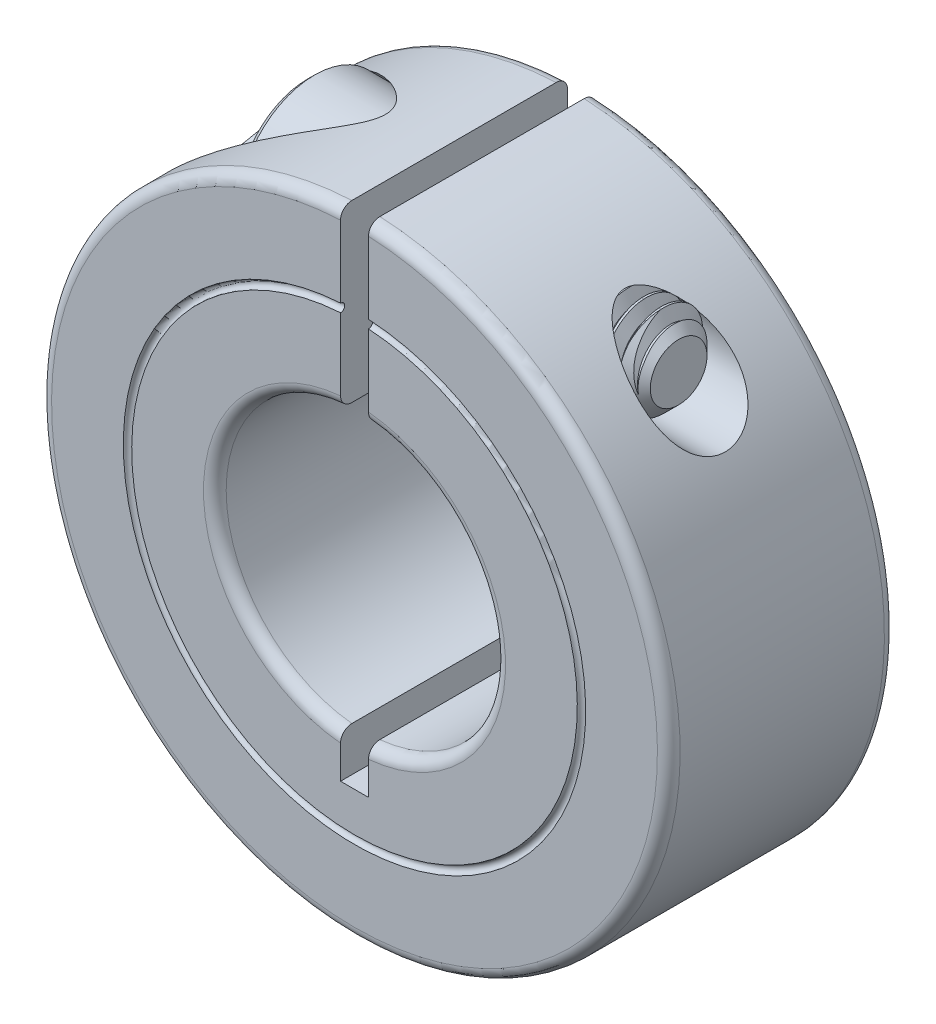
SolidWorks part; units mm, degrees
ref_plane "Front Plane" through (0, 0, 0) normal (0, 0, 1) x (1, 0, 0)
ref_plane "Top Plane" through (0, 0, 0) normal (0, 1, 0) x (1, 0, 0)
ref_plane "Right Plane" through (0, 0, 0) normal (1, 0, 0) x (0, 0, -1)
sketch "Sketch1" plane through (0, 0, 0) normal (0, 0, 1) x (1, 0, 0)
  line L0 (-0.635, 6.3182) -> (-0.635, 14.2734)
  line L2 (0.635, 6.3182) -> (0.635, 14.2734)
  line L3 (0, 0) -> (0, 6.3182) construction
  line L4 (0.635, 6.3182) -> (-0.635, 6.3182) construction
  line L5 (0, -14.2875) -> (0, -6.35) construction
  line L6 (0, -6.35) -> (0, -10.3188) construction
  line L7 (-0.635, -6.3182) -> (-0.635, -8.3344)
  line L8 (-0.635, -8.3344) -> (0.635, -8.3344)
  line L9 (0.635, -6.3182) -> (0.635, -8.3344)
  line L10 (-0.635, 10.2958) -> (0.635, 10.2958) construction
  circle A0 centre (0, 0) radius 14.2875 construction
  circle A1 centre (0, 0) radius 6.35 construction
  arc A3 (-0.635, 14.2734) -> (0.635, 14.2734) centre (0, 0) ccw
  arc A4 (0.635, -6.3182) -> (0.635, 6.3182) centre (0, 0) ccw
  arc A5 (-0.635, 6.3182) -> (-0.635, -6.3182) centre (0, 0) ccw
  point P4 (14.2875, 0)
  point P5 (-14.2875, 0)
  point P19 (0, -8.3344)
  dimension "Bore Dia" = 12.7
  dimension "OD" = 28.575
  dimension "Separation" = 1.27
extrude "Extrude1" add sketch "Sketch1" along normal mid plane 10.3187
fillet "Fillet1" radius 0.5159 6 edges at (0, -14.2875, -5.1594) (0, -14.2875, 5.1594) (-6.35, 0, 5.1594) (-6.35, 0, -5.1594) (6.35, 0, 5.1594) (6.35, 0, -5.1594)
sketch "Sketch2" plane through (0, 0, 0) normal (0, 1, 0) x (1, 0, 0)
  line L0 (0, 0) -> (-6.35, 0) construction
  line L1 (-6.35, 0) -> (-14.2875, 0) construction
  line L2 (-10.3188, 5.1594) -> (-10.3188, -5.1594) construction
  line L3 (13.7716, 5.1594) -> (-13.7716, 5.1594) construction
  line L4 (-13.7716, -5.1594) -> (13.7716, -5.1594) construction
  line L5 (-14.2875, 4.6434) -> (-14.2875, -4.6434) construction
  line L6 (-6.35, 4.6434) -> (-6.35, -4.6434) construction
  line L8 (-10.5092, -5.1594) -> (-10.1283, -5.1594)
  line L9 (0, 5.1594) -> (0, -5.1594) construction
  line L10 (-0.635, 5.1594) -> (-6.8659, 5.1594) construction
  arc A1 (-10.1283, -5.1594) -> (-10.5092, -5.1594) centre (-10.3188, -5.1594) ccw
  point P1 (-10.3188, 0)
  dimension "D2" = 0.1905
revolve "Cut-Revolve1" cut sketch "Sketch2" angle 360 about L9
sketch "Sketch3" plane through (0, 0, 0) normal (0, 0, 1) x (1, 0, 0)
  line L0 (14.2875, 10.2958) -> (-14.2875, 10.2958)
  line L1 (-14.2875, 10.2958) -> (-14.2875, 6.8033)
  line L2 (-14.2875, 6.8033) -> (-3.1242, 6.8033)
  line L4 (-3.1242, 6.8033) -> (-3.1242, 8.213)
  line L7 (-3.1242, 8.213) -> (14.2875, 8.213)
  line L8 (14.2875, 8.213) -> (14.2875, 10.2958)
  line L9 (-14.2875, 10.2958) -> (-17.78, 10.2958) construction
  line L10 (-0.635, 10.2958) -> (0.635, 10.2958) construction
  dimension "D2" = 3.1242
  dimension "D4" = 6.985
  dimension "Screw Dia" = 4.1656
revolve "Cut-Revolve2" cut sketch "Sketch3" angle 360 about L9
sketch "Sketch4" plane through (0, 0, 0) normal (0, 0, 1) x (1, 0, 0)
  line L0 (-7.2898, 10.2958) -> (-7.2898, 13.7248)
  line L2 (-7.2898, 13.7248) -> (-3.1242, 13.7248)
  line L3 (-3.1242, 13.7248) -> (-3.1242, 12.3786)
  line L4 (-3.1242, 12.3786) -> (9.5758, 12.3786)
  line L5 (-3.1242, 6.8033) -> (-3.1242, 8.213) construction
  line L6 (9.5758, 12.3786) -> (9.5758, 10.2958)
  line L7 (-3.1242, 8.213) -> (14.2875, 8.213) construction
  line L8 (9.5758, 10.2958) -> (-7.2898, 10.2958)
  line L9 (9.5758, 12.3786) -> (9.5758, 8.213) construction
  line L10 (-7.2898, 10.2958) -> (-10.7188, 10.2958) construction
  line L11 (-14.2875, 10.2958) -> (-17.78, 10.2958) construction
  dimension "Head Ht" = 4.1656
  dimension "Screw Lg" = 12.7
  dimension "Head Dia" = 6.858
revolve "Revolve1" add sketch "Sketch4" angle 360 about L8
sketch "Sketch5" plane through (-7.2898, 0, 0) normal (-1, 0, 0) x (0, -1, 0)
  line L1 (-9.2647, -1.7859) -> (-8.2336, 0)
  line L2 (-8.2336, 0) -> (-9.2647, 1.7859)
  line L3 (-9.2647, 1.7859) -> (-11.3269, 1.7859)
  line L4 (-11.3269, 1.7859) -> (-12.358, 0)
  line L5 (-12.358, 0) -> (-11.3269, -1.7859)
  line L6 (-11.3269, -1.7859) -> (-9.2647, -1.7859)
  circle A0 centre (-10.2958, 0) radius 1.7859 construction
  dimension "Hex" = 3.5719
extrude "Cut-Extrude1" cut sketch "Sketch5" against normal blind 3.5719
chamfer "Chamfer1" distance 0.3175 angle 45 1 edges at (-7.2898, 13.7248, 0)
sketch "Sketch6" plane through (9.5758, 0, 0) normal (1, 0, 0) x (0, 1, 0)
  circle A0 centre (10.2958, 0) radius 2.0828 construction
  circle A1 centre (10.2958, 0) radius 2.0828
  point P3 (12.3786, 0)
curve "Helix/Spiral1" pitch 0.7937 height 12.7 turns 16 parameters "Height"=12.7, "Pitch"=0.7937
sketch "Sketch7" plane through (0, 0, 0) normal (0, 0, 1) x (1, 0, 0)
  line L0 (9.9231, 11.7771) -> (9.5262, 12.4645) construction
  line L1 (9.5262, 12.4645) -> (10.3199, 12.4645) construction
  line L2 (10.3199, 12.4645) -> (9.9231, 11.7771) construction
  line L3 (9.5758, 12.3786) -> (10.2703, 12.3786) construction
  line L4 (9.8735, 11.863) -> (9.9727, 11.863)
  line L5 (9.9231, 12.4645) -> (9.9231, 12.3786) construction
  line L6 (9.9231, 11.863) -> (9.9231, 11.7771) construction
  line L7 (9.8735, 11.863) -> (9.551, 12.4215)
  line L8 (9.551, 12.4215) -> (10.2951, 12.4215)
  line L9 (10.2951, 12.4215) -> (9.9727, 11.863)
  point P10 (9.9231, 12.4215)
  dimension "D1" = 0.7937
  dimension "D2" = 0.0992
chamfer "Chamfer2" distance 0.7937 angle 45 1 edges at (9.5758, 12.3786, 0)
sweep "Cut-Sweep1" cut profiles "Sketch7" path "Helix/Spiral1"
equation "\"D1@Sketch3\" = \"Screw Dia@Sketch3\""
equation "\"D1@Cut-Extrude1\" = \"Hex@Sketch5\""
equation "\"D1@Fillet1\" = \"Width@Extrude1\"*.05"
equation "\"D4@Sketch3\" = \"Head Dia@Sketch4\" + .005"
equation "\"Height@Helix/Spiral1\" = \"Screw Lg@Sketch4\""
equation "\"D1@Sketch7\" = \"Pitch@Helix/Spiral1\""
equation "\"D2@Sketch7\" = \"D1@Sketch7\"/8"
equation "\"D1@Chamfer2\" = \"Pitch@Helix/Spiral1\""
equation "\"Separation@Sketch1\" = \"Bore Dia@Sketch1\"/10"
equation "\"D2@Sketch3\" = \"Screw Dia@Sketch3\"*.750"
